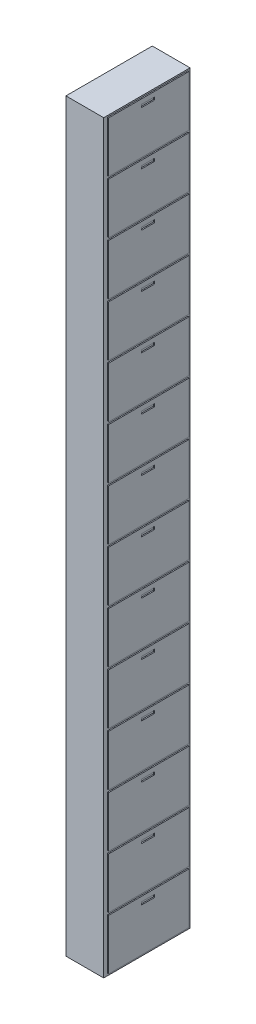
SolidWorks part; units mm, degrees
ref_plane "Front Plane" through (0, 0, 0) normal (0, 0, 1) x (1, 0, 0)
ref_plane "Top Plane" through (0, 0, 0) normal (0, 1, 0) x (1, 0, 0)
ref_plane "Right Plane" through (0, 0, 0) normal (1, 0, 0) x (0, 0, -1)
sketch "Sketch1" plane through (0, 0, 0) normal (0, 0, 1) x (1, 0, 0)
  line L0 (213.062, 4179.9863) -> (-136.938, 4179.9863)
  line L1 (-136.938, 4179.9863) -> (-136.938, -2720.0137)
  line L2 (-136.938, -2720.0137) -> (213.062, -2720.0137)
  line L5 (213.062, -2720.0137) -> (213.062, 4179.9863)
  dimension "D1" = 350
  dimension "D2" = 6900
extrude "Boss-Extrude1" add sketch "Sketch1" along normal blind 800
sketch "Sketch3" plane through (213.062, 0, 0) normal (1, 0, 0) x (0, 0, -1)
  line L0 (0, -2720.0137) -> (0, 4179.9863) construction
  line L1 (-763.6321, -2700.0137) -> (-20, -2700.0137)
  line L2 (-763.6321, -2700.0137) -> (-763.6321, -2230.0137)
  line L3 (-763.6321, -2230.0137) -> (-20, -2230.0137)
  line L4 (-20, -2700.0137) -> (-20, -2230.0137)
  line L5 (-800, -2720.0137) -> (0, -2720.0137) construction
  line L6 (-763.6321, -2208.0137) -> (-20, -2208.0137)
  line L7 (-461.6648, -2274.1108) -> (-340.5919, -2274.1108)
  line L8 (-461.6648, -2274.1108) -> (-461.6648, -2299.9132)
  line L9 (-461.6648, -2299.9132) -> (-340.5919, -2299.9132)
  line L10 (-340.5919, -2274.1108) -> (-340.5919, -2299.9132)
  line L11 (-763.6321, -2208.0137) -> (-763.6321, -1738.0137)
  line L12 (-763.6321, -1738.0137) -> (-20, -1738.0137)
  line L13 (-20, -2208.0137) -> (-20, -1738.0137)
  line L14 (-461.6648, -1782.1108) -> (-340.5919, -1782.1108)
  line L15 (-461.6648, -1807.9132) -> (-340.5919, -1807.9132)
  line L16 (-461.6648, -1782.1108) -> (-461.6648, -1807.9132)
  line L17 (-340.5919, -1782.1108) -> (-340.5919, -1807.9132)
  line L18 (-763.6321, -1716.0137) -> (-20, -1716.0137)
  line L19 (-763.6321, -1716.0137) -> (-763.6321, -1246.0137)
  line L20 (-763.6321, -1246.0137) -> (-20, -1246.0137)
  line L21 (-20, -1716.0137) -> (-20, -1246.0137)
  line L22 (-461.6648, -1290.1108) -> (-340.5919, -1290.1108)
  line L23 (-461.6648, -1315.9132) -> (-340.5919, -1315.9132)
  line L24 (-461.6648, -1290.1108) -> (-461.6648, -1315.9132)
  line L25 (-340.5919, -1290.1108) -> (-340.5919, -1315.9132)
  line L26 (-763.6321, -1224.0137) -> (-20, -1224.0137)
  line L27 (-763.6321, -1224.0137) -> (-763.6321, -754.0137)
  line L28 (-763.6321, -754.0137) -> (-20, -754.0137)
  line L29 (-20, -1224.0137) -> (-20, -754.0137)
  line L30 (-461.6648, -798.1108) -> (-340.5919, -798.1108)
  line L31 (-461.6648, -823.9132) -> (-340.5919, -823.9132)
  line L34 (-461.6648, -798.1108) -> (-461.6648, -823.9132)
  line L35 (-340.5919, -798.1108) -> (-340.5919, -823.9132)
  line L36 (-763.6321, -732.0137) -> (-20, -732.0137)
  line L37 (-763.6321, -732.0137) -> (-763.6321, -262.0137)
  line L38 (-763.6321, -262.0137) -> (-20, -262.0137)
  line L39 (-20, -732.0137) -> (-20, -262.0137)
  line L40 (-461.6648, -306.1108) -> (-340.5919, -306.1108)
  line L41 (-461.6648, -331.9132) -> (-340.5919, -331.9132)
  line L42 (-461.6648, -306.1108) -> (-461.6648, -331.9132)
  line L43 (-340.5919, -306.1108) -> (-340.5919, -331.9132)
  line L44 (-763.6321, -240.0137) -> (-20, -240.0137)
  line L45 (-763.6321, -240.0137) -> (-763.6321, 229.9863)
  line L46 (-763.6321, 229.9863) -> (-20, 229.9863)
  line L47 (-20, -240.0137) -> (-20, 229.9863)
  line L48 (-461.6648, 185.8892) -> (-340.5919, 185.8892)
  line L49 (-461.6648, 160.0868) -> (-340.5919, 160.0868)
  line L50 (-461.6648, 185.8892) -> (-461.6648, 160.0868)
  line L51 (-340.5919, 185.8892) -> (-340.5919, 160.0868)
  line L52 (-763.6321, 251.9863) -> (-20, 251.9863)
  line L53 (-763.6321, 251.9863) -> (-763.6321, 721.9863)
  line L54 (-763.6321, 721.9863) -> (-20, 721.9863)
  line L55 (-20, 251.9863) -> (-20, 721.9863)
  line L56 (-461.6648, 677.8892) -> (-340.5919, 677.8892)
  line L57 (-461.6648, 652.0868) -> (-340.5919, 652.0868)
  line L58 (-461.6648, 677.8892) -> (-461.6648, 652.0868)
  line L59 (-340.5919, 677.8892) -> (-340.5919, 652.0868)
  line L60 (-763.6321, 743.9863) -> (-20, 743.9863)
  line L61 (-763.6321, 743.9863) -> (-763.6321, 1213.9863)
  line L62 (-763.6321, 1213.9863) -> (-20, 1213.9863)
  line L63 (-20, 743.9863) -> (-20, 1213.9863)
  line L64 (-461.6648, 1169.8892) -> (-340.5919, 1169.8892)
  line L65 (-461.6648, 1144.0868) -> (-340.5919, 1144.0868)
  line L66 (-461.6648, 1169.8892) -> (-461.6648, 1144.0868)
  line L67 (-340.5919, 1169.8892) -> (-340.5919, 1144.0868)
  line L68 (-763.6321, 1235.9863) -> (-20, 1235.9863)
  line L69 (-763.6321, 1235.9863) -> (-763.6321, 1705.9863)
  line L70 (-763.6321, 1705.9863) -> (-20, 1705.9863)
  line L71 (-20, 1235.9863) -> (-20, 1705.9863)
  line L72 (-461.6648, 1661.8892) -> (-340.5919, 1661.8892)
  line L73 (-461.6648, 1636.0868) -> (-340.5919, 1636.0868)
  line L74 (-461.6648, 1661.8892) -> (-461.6648, 1636.0868)
  line L75 (-340.5919, 1661.8892) -> (-340.5919, 1636.0868)
  line L76 (-763.6321, 1727.9863) -> (-20, 1727.9863)
  line L77 (-763.6321, 1727.9863) -> (-763.6321, 2197.9863)
  line L78 (-763.6321, 2197.9863) -> (-20, 2197.9863)
  line L79 (-20, 1727.9863) -> (-20, 2197.9863)
  line L80 (-461.6648, 2153.8892) -> (-340.5919, 2153.8892)
  line L81 (-461.6648, 2128.0868) -> (-340.5919, 2128.0868)
  line L82 (-461.6648, 2153.8892) -> (-461.6648, 2128.0868)
  line L83 (-340.5919, 2153.8892) -> (-340.5919, 2128.0868)
  line L84 (-763.6321, 2219.9863) -> (-20, 2219.9863)
  line L85 (-763.6321, 2219.9863) -> (-763.6321, 2689.9863)
  line L86 (-763.6321, 2689.9863) -> (-20, 2689.9863)
  line L87 (-20, 2219.9863) -> (-20, 2689.9863)
  line L88 (-461.6648, 2645.8892) -> (-340.5919, 2645.8892)
  line L89 (-461.6648, 2620.0868) -> (-340.5919, 2620.0868)
  line L90 (-461.6648, 2645.8892) -> (-461.6648, 2620.0868)
  line L91 (-340.5919, 2645.8892) -> (-340.5919, 2620.0868)
  line L92 (-763.6321, 2711.9863) -> (-20, 2711.9863)
  line L93 (-763.6321, 2711.9863) -> (-763.6321, 3181.9863)
  line L94 (-763.6321, 3181.9863) -> (-20, 3181.9863)
  line L95 (-20, 2711.9863) -> (-20, 3181.9863)
  line L96 (-461.6648, 3137.8892) -> (-340.5919, 3137.8892)
  line L97 (-461.6648, 3112.0868) -> (-340.5919, 3112.0868)
  line L98 (-461.6648, 3137.8892) -> (-461.6648, 3112.0868)
  line L99 (-340.5919, 3137.8892) -> (-340.5919, 3112.0868)
  line L100 (-763.6321, 3203.9863) -> (-20, 3203.9863)
  line L101 (-763.6321, 3203.9863) -> (-763.6321, 3673.9863)
  line L102 (-763.6321, 3673.9863) -> (-20, 3673.9863)
  line L103 (-20, 3203.9863) -> (-20, 3673.9863)
  line L104 (-461.6648, 3629.8892) -> (-340.5919, 3629.8892)
  line L105 (-461.6648, 3604.0868) -> (-340.5919, 3604.0868)
  line L106 (-461.6648, 3629.8892) -> (-461.6648, 3604.0868)
  line L107 (-340.5919, 3629.8892) -> (-340.5919, 3604.0868)
  line L108 (-763.6321, 3695.9863) -> (-20, 3695.9863)
  line L109 (-763.6321, 3695.9863) -> (-763.6321, 4165.9863)
  line L110 (-763.6321, 4165.9863) -> (-20, 4165.9863)
  line L111 (-20, 3695.9863) -> (-20, 4165.9863)
  line L112 (-461.6648, 4121.8892) -> (-340.5919, 4121.8892)
  line L113 (-461.6648, 4096.0868) -> (-340.5919, 4096.0868)
  line L114 (-461.6648, 4121.8892) -> (-461.6648, 4096.0868)
  line L115 (-340.5919, 4121.8892) -> (-340.5919, 4096.0868)
  dimension "D1" = 470
  dimension "D2" = 20
  dimension "D3" = 20
  dimension "D4" = 14
extrude "Boss-Extrude3" add sketch "Sketch3" along normal blind 10 contours L1 L4 L3 L2 L7 L10 L9 L8 | L18 L21 L20 L19 L22 L25 L23 L24 | L6 L13 L12 L11 L14 L17 L15 L16 | L26 L29 L28 L27 L30 L35 L31 L34 | L36 L39 L38 L37 L40 L43 L41 L42 | L44 L47 L46 L45 L48 L51 L49 L50 | L52 L55 L54 L53 L56 L59 L57 L58 | L60 L63 L62 L61 L64 L67 L65 L66 | L68 L71 L70 L69 L72 L75 L73 L74 | L76 L79 L78 L77 L80 L83 L81 L82 | L84 L87 L86 L85 L88 L91 L89 L90 | L92 L95 L94 L93 L96 L99 L97 L98 | L100 L103 L102 L101 L104 L107 L105 L106 | L108 L111 L110 L109 L112 L115 L113 L114 region at (213.062, -2466.619, 391.732) region at (213.062, -1974.619, 391.732) region at (213.062, -1482.619, 391.732) region at (213.062, -990.619, 391.732) region at (213.062, -498.619, 391.732) region at (213.062, -6.619, 391.732) region at (213.062, 485.381, 391.732) region at (213.062, 977.381, 391.732) region at (213.062, 1469.381, 391.732) region at (213.062, 1961.381, 391.732) region at (213.062, 2453.381, 391.732) region at (213.062, 2945.381, 391.732) region at (213.062, 3437.381, 391.732) region at (213.062, 3929.381, 391.732)
